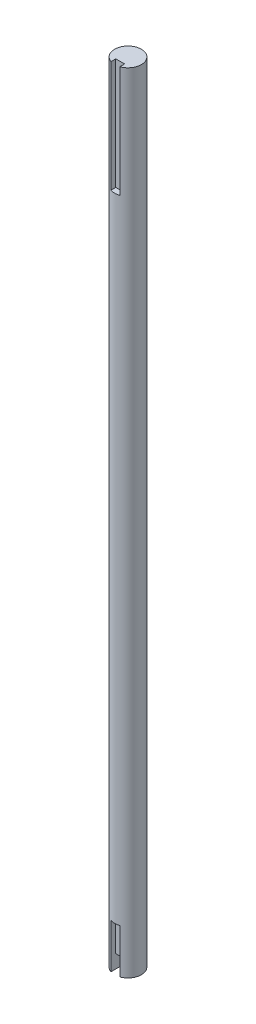
SolidWorks part; units mm, degrees
ref_plane "Front Plane" through (0, 0, 0) normal (0, 0, 1) x (1, 0, 0)
ref_plane "Top Plane" through (0, 0, 0) normal (0, 1, 0) x (1, 0, 0)
ref_plane "Right Plane" through (0, 0, 0) normal (1, 0, 0) x (0, 0, -1)
sketch "Sketch1" plane through (0, 0, 0) normal (0, 1, 0) x (1, 0, 0)
  circle A0 centre (0, 0) radius 6
  dimension "D1" = 12
extrude "Boss-Extrude1" add sketch "Sketch1" along normal blind 254 and the other way blind 100
sketch "Sketch2" plane through (0, 0, 0) normal (0, 1, 0) x (1, 0, 0)
  line L1 (-2, -8.5) -> (2, -8.5)
  line L2 (-2, -8.5) -> (-2, -3.5)
  line L3 (-2, -3.5) -> (2, -3.5)
  line L4 (2, -8.5) -> (2, -3.5)
  line L5 (-2, -8.5) -> (2, -3.5) construction
  line L6 (-2, -3.5) -> (2, -8.5) construction
  circle A0 centre (0, 0) radius 6 construction
  point P0 (0, -6)
  dimension "D1" = 2.5
  dimension "D2" = 4
extrude "Cut-Extrude3" cut sketch "Sketch2" against normal blind 0.0001 and the other way blind 20 from surface starting at face at (0, -100, 6)
extrude "Cut-Extrude4" cut sketch "Sketch2<2>" against normal blind 50 from surface starting at face at (0, 254, 6)
sketch "Sketch2<2>" plane through (0, 0, 0) normal (0, 1, 0) x (1, 0, 0) same geometry as "Sketch2"
sketch "Sketch3" plane through (0, 0, 0) normal (0, 1, 0) x (1, 0, 0)
  line L1 (-2, -11) -> (2, -11)
  line L2 (-2, -11) -> (-2, -1)
  line L3 (-2, -1) -> (2, -1)
  line L4 (2, -11) -> (2, -1)
  line L5 (-2, -11) -> (2, -1) construction
  line L6 (-2, -1) -> (2, -11) construction
  arc A0 (-2, -5.6569) -> (2, -5.6569) centre (0, 0) ccw construction
  point P0 (0, -6)
  dimension "D1" = 4
  dimension "D2" = 5
extrude "Cut-Extrude6" cut sketch "Sketch3" along normal blind 6 from surface starting at face at (0, -100, 1.6642)
sketch "Sketch5" plane through (0, 0, 0) normal (1, 0, 0) x (0, 0, -1)
  line L0 (0, 259.1669) -> (0, -132.9751) construction
